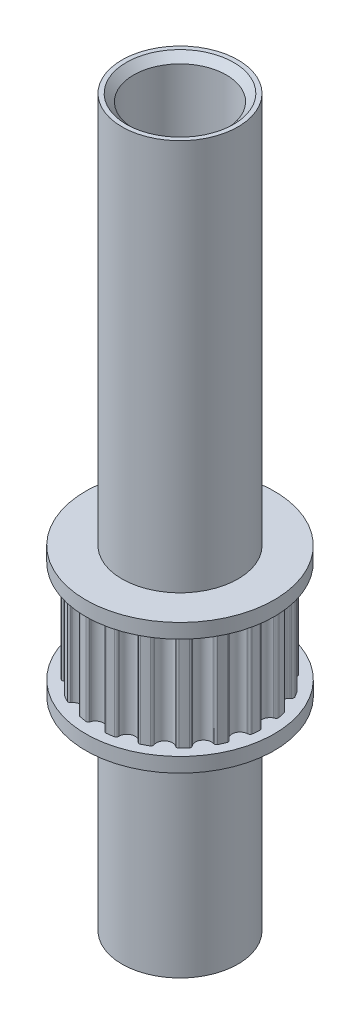
SolidWorks part; units mm, degrees
ref_plane "Front Plane" through (0, 0, 0) normal (0, 0, 1) x (1, 0, 0)
ref_plane "Top Plane" through (0, 0, 0) normal (0, 1, 0) x (1, 0, 0)
ref_plane "Right Plane" through (0, 0, 0) normal (1, 0, 0) x (0, 0, -1)
sketch "Sketch1" plane through (0, 0, 0) normal (0, 1, 0) x (1, 0, 0)
  circle A0 centre (0, 0) radius 4
  circle A1 centre (0, 0) radius 3.2
  dimension "D1" = 8
  dimension "D2" = 0.8
extrude "Boss-Extrude1" add sketch "Sketch1" along normal blind 50
ref_plane "Plane1" through (0, 15, 0) normal (0, 1, 0) x (1, 0, 0)
sketch "Sketch2" plane through (0, 15, 0) normal (0, 1, 0) x (1, 0, 0)
  circle A0 centre (0, 0) radius 6
  circle A1 centre (0, 0) radius 4
  dimension "D1" = 12
extrude "Boss-Extrude2" add sketch "Sketch2" along normal blind 7
sketch "Sketch3" plane through (0, 15, 0) normal (0, -1, 0) x (1, 0, 0)
  circle A0 centre (0, 0) radius 4
  circle A1 centre (0, 0) radius 6.5
  circle A2 centre (0, 0) radius 4 construction
  dimension "D1" = 13
extrude "Boss-Extrude3" add sketch "Sketch3" along normal blind 1 separate body
sketch "Sketch6" plane through (0, 15, 0) normal (0, 1, 0) x (1, 0, 0)
  line L0 (0, 0) -> (0, 8.1681) construction
  line L1 (-0.0071, -0.0407) -> (0.9465, 5.4303) construction
  line L2 (-0.0099, -0.04) -> (1.3906, 5.6439) construction
  line L3 (0, 5.795) -> (0, 6.6155)
  line L4 (1.9605, 5.4533) -> (2.2381, 6.2254)
  arc A1 (0.2982, 5.7873) -> (0, 5.795) centre (0, 0) ccw
  arc A2 (0.2982, 5.7873) -> (0.439, 5.6587) centre (0.2905, 5.6375) cw
  arc A3 (0.439, 5.6587) -> (0.4521, 5.586) centre (1.429, 5.7996) ccw
  arc A4 (0.4521, 5.586) -> (1.4644, 5.4096) centre (0.9943, 5.7045) ccw
  circle A5 centre (0, 0) radius 5.2355 construction
  circle A6 centre (0, 0) radius 5.795 construction
  arc A7 (-1.5827, -6.4234) -> (-1.1359, -6.5173) centre (0, 0) ccw
  arc A8 (1.5013, 5.4735) -> (1.4644, 5.4096) centre (0.6173, 5.941) cw
  arc A9 (1.6773, 5.5469) -> (1.5013, 5.4735) centre (1.6339, 5.4034) ccw
  arc A10 (1.6773, 5.5469) -> (1.9605, 5.4533) centre (0, 0) cw
  arc A11 (2.2381, 6.2254) -> (0, 6.6155) centre (0, 0) ccw
  circle A12 centre (0, 0) radius 6.6155 construction
  point P15 (1.3864, 5.6267)
  point P16 (0.995, 5.7089)
  point P18 (6.3265, 1.9342)
  dimension "D1" = 1.38
  dimension "D2" = 0.15
  dimension "D3" = 1
  dimension "D4" = 0.555
  dimension "D7" = 11.59
  dimension "D6" = 0.4
  dimension "D5" = 1.38
  dimension "D8" = 1
extrude "Cut-Extrude1" cut sketch "Sketch6" along normal blind 7 contours L4 A11 L3 A1 A2 A3 A4 A8 A9 A10 region at (1.0383, 15, -5.9574)
ref_axis "Axis1" through (0, 50, 0) along (0, -1, 0)
pattern_circular "CirPattern1" count 19 over 360 about axis through (0, 50, 0) along (0, -1, 0) of "Cut-Extrude1"
sketch "Sketch4" plane through (0, 22, 0) normal (0, 1, 0) x (1, 0, 0)
  circle A0 centre (0, 0) radius 6.5
  circle A1 centre (0, 0) radius 4
  dimension "D1" = 13
extrude "Boss-Extrude4" add sketch "Sketch4" along normal blind 1
chamfer "Chamfer1" distance 0.5 angle 45 2 edges at (0, 50, 3.2) (0, 0, 3.2)
